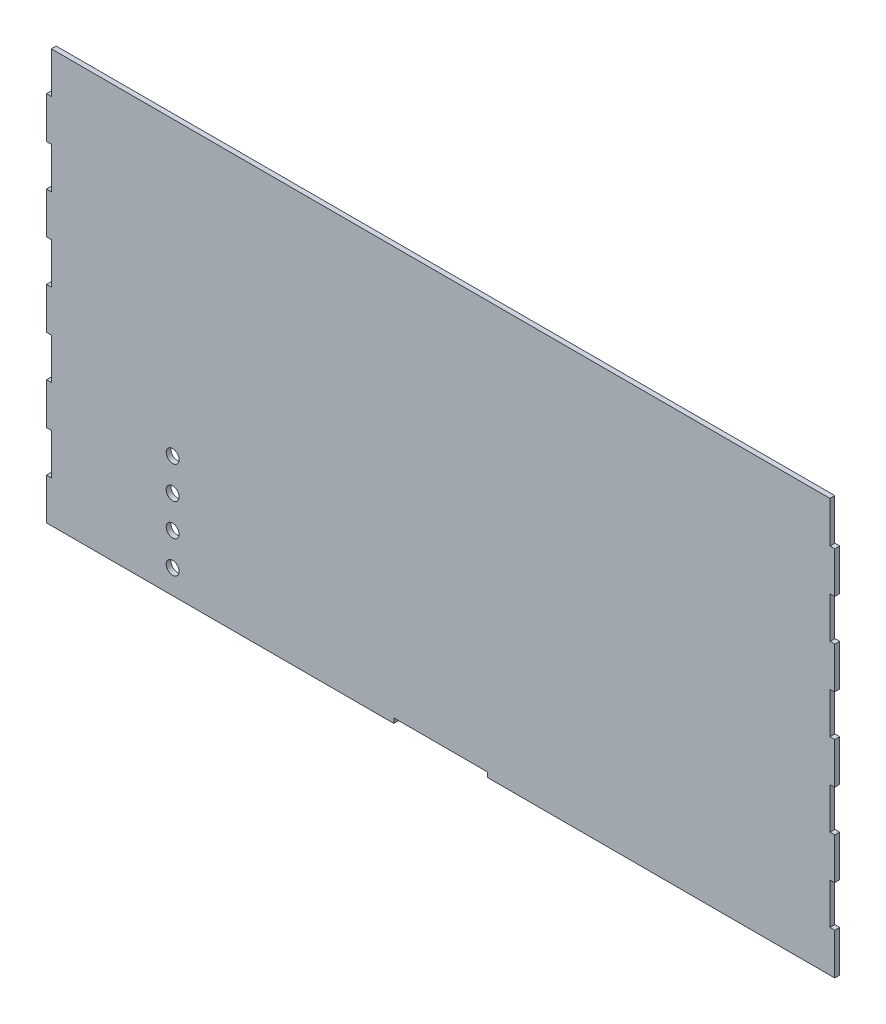
SolidWorks part; units mm, degrees
material "Pine"
ref_plane "Front Plane" through (0, 0, 0) normal (0, 0, 1) x (1, 0, 0)
ref_plane "Top Plane" through (0, 0, 0) normal (0, 1, 0) x (1, 0, 0)
ref_plane "Right Plane" through (0, 0, 0) normal (1, 0, 0) x (0, 0, -1)
sketch "Sketch1" plane through (0, 0, 0) normal (0, 0, 1) x (1, 0, 0)
  line L1 (-488.6875, 256) -> (488.6875, 256)
  line L2 (-488.6875, 256) -> (-488.6875, -256)
  line L3 (-488.6875, -256) -> (488.6875, -256)
  line L4 (488.6875, 256) -> (488.6875, -256)
  line L5 (-488.6875, 256) -> (488.6875, -256) construction
  line L6 (-488.6875, -256) -> (488.6875, 256) construction
  point P4 (0, 0)
  dimension "D1" = 977.375
  dimension "D2" = 512
  dimension "D3" = 0
  dimension "D4" = 0
extrude "Boss-Extrude1" add sketch "Sketch1" along normal blind 6
sketch "Sketch7" plane through (0, 0, 6) normal (0, 0, 1) x (1, 0, 0)
  line L0 (488.6875, -256) -> (488.6875, 256) construction
  line L1 (488.6875, -204.8) -> (482.6875, -204.8)
  line L2 (488.6875, -204.8) -> (488.6875, -153.6)
  line L3 (488.6875, -153.6) -> (482.6875, -153.6)
  line L4 (482.6875, -204.8) -> (482.6875, -153.6)
  line L5 (-488.6875, -256) -> (488.6875, -256) construction
  ellipse E0 centre (485.6875, -204.8) end of major axis (488.6875, -204.8) minor radius 0.2
  ellipse E1 centre (485.6875, -153.6) end of major axis (488.6875, -153.6) minor radius 0.2
  line M8 (488.6875, -256) -> (488.6875, 256)
  dimension "D1" = 6
  dimension "D2" = 51.2
  dimension "D3" = 51.2
  dimension "D4" = 0.2
  dimension "D5" = 0.2
extrude "Cut-Extrude3" cut sketch "Sketch7" against normal blind 10 contours E0 L3 L4 M8 region at (485.6875, -179.2, 6)
pattern_linear "LPattern1" count 5 spacing 102.4 along (0, 1, 0) of "Cut-Extrude3"
sketch "Sketch8" plane through (0, 0, 6) normal (0, 0, 1) x (1, 0, 0)
  line L1 (482.6875, 256) -> (488.6875, 256)
  line L2 (482.6875, 256) -> (482.6875, 255.4193)
  line L3 (482.6875, 255.4193) -> (488.6875, 255.4193)
  line L4 (488.6875, 256) -> (488.6875, 255.4193)
  dimension "D1" = 6
  dimension "D2" = 0.5807
extrude "Cut-Extrude4" cut sketch "Sketch8" against normal blind 10
sketch "Sketch10" plane through (0, 0, 6) normal (0, 0, 1) x (1, 0, 0)
  line L0 (-488.6875, 256) -> (-488.6875, -256) construction
  line L1 (-488.6875, -204.8) -> (-482.6875, -204.8)
  line L2 (-488.6875, -204.8) -> (-488.6875, -153.6)
  line L3 (-488.6875, -153.6) -> (-482.6875, -153.6)
  line L4 (-482.6875, -204.8) -> (-482.6875, -153.6)
  line L5 (-488.6875, -256) -> (488.6875, -256) construction
  ellipse E0 centre (-485.6875, -204.8) end of major axis (-482.6875, -204.8) minor radius 0.2
  ellipse E1 centre (-485.6875, -153.6) end of major axis (-482.6875, -153.6) minor radius 0.2
  line M18 (-488.6875, 256) -> (-488.6875, -256)
  dimension "D1" = 6
  dimension "D2" = 102.4
  dimension "D3" = 51.2
  dimension "D4" = 0.2
  dimension "D5" = 0.2
extrude "Cut-Extrude5" cut sketch "Sketch10" against normal blind 10 contours E1 E0 L4 M18 region at (-485.6875, -179.2, 6)
pattern_linear "LPattern4" count 5 spacing 102.4 along (0, 1, 0) of "Cut-Extrude5"
sketch "Sketch11" plane through (0, 0, 6) normal (0, 0, 1) x (1, 0, 0)
  line L1 (-482.6875, 256) -> (-488.6875, 256)
  line L2 (-482.6875, 256) -> (-482.6875, 255.2668)
  line L3 (-482.6875, 255.2668) -> (-488.6875, 255.2668)
  line L4 (-488.6875, 256) -> (-488.6875, 255.2668)
  dimension "D1" = 6
  dimension "D2" = 0.7332
extrude "Cut-Extrude6" cut sketch "Sketch11" against normal blind 10 contours L3 L4 L1 L2
sketch "Sketch12" plane through (0, 0, 6) normal (0, 0, 1) x (1, 0, 0)
  line L0 (282.1875, 256) -> (282.1875, -256)
  line L1 (482.6875, 256) -> (-482.6875, 256) construction
  line L2 (-488.6875, -256) -> (488.6875, -256) construction
  line L3 (488.6875, 153.6) -> (488.6875, 204.8) construction
  line L4 (-282.1875, 256) -> (-282.1875, -256)
  line L5 (-488.6875, 204.8) -> (-488.6875, 153.6) construction
  line L6 (-206, 256) -> (-206, -256)
  dimension "D1" = 206.5
  dimension "D2" = 206.5
  dimension "D3" = 206
sketch "Sketch13" plane through (0, 0, 6) normal (0, 0, 1) x (1, 0, 0)
  line L0 (206, 256) -> (206, -256)
  line L1 (482.6875, 256) -> (-482.6875, 256) construction
  line L2 (-488.6875, -256) -> (488.6875, -256) construction
  dimension "D1" = 206
sketch "Sketch14" plane through (0, 0, 6) normal (0, 0, 1) x (1, 0, 0)
  line L1 (-58, -250.0304) -> (58, -250.0304)
  line L2 (-58, -250.0304) -> (-58, -256.0304)
  line L3 (-58, -256.0304) -> (58, -256.0304)
  line L4 (58, -250.0304) -> (58, -256.0304)
  line L5 (-58, -250.0304) -> (58, -256.0304) construction
  line L6 (-58, -256.0304) -> (58, -250.0304) construction
  point P4 (0, -253.0304)
  dimension "D1" = 148
  dimension "D2" = 148
extrude "Cut-Extrude9" cut sketch "Sketch14" against normal blind 10 contours L2 L1 L4 L3
sketch "Sketch15" plane through (0, 0, 6) normal (0, 0, 1) x (1, 0, 0)
  line L0 (-488.6875, -256) -> (-58, -256) construction
  line L1 (-282.1875, 256) -> (-282.1875, -256) construction
  circle A0 centre (-332.1875, -226) radius 8
  dimension "D1" = 30
  dimension "D2" = 50
extrude "Cut-Extrude11" cut sketch "Sketch15" against normal blind 10
pattern_linear "LPattern5" count 4 spacing 40 along (0, 1, 0) of "Cut-Extrude11"
